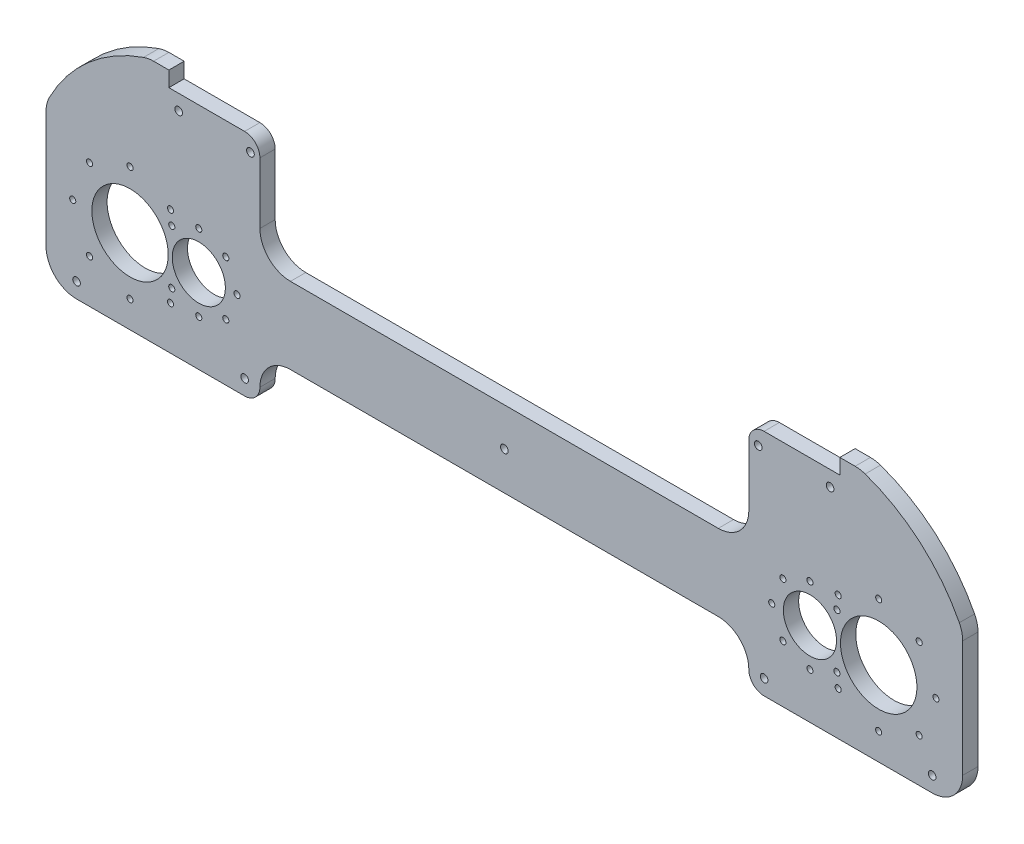
SolidWorks part; units mm, degrees
material "ABS"
ref_plane "Front Plane" through (0, 0, 0) normal (0, 0, 1) x (1, 0, 0)
ref_plane "Top Plane" through (0, 0, 0) normal (0, 1, 0) x (1, 0, 0)
ref_plane "Right Plane" through (0, 0, 0) normal (1, 0, 0) x (0, 0, -1)
sketch "Sketch1" plane through (0, 0, 0) normal (0, 0, 1) x (1, 0, 0)
  line L0 (-145.7836, 66.675) -> (145.7836, 66.675)
  line L1 (-190.5, 26.1817) -> (-190.5, -22.225)
  line L4 (0, 0) -> (0, 100.7987) construction
  line L5 (-177.8, -34.925) -> (177.8, -34.925)
  line L6 (190.5, 26.1817) -> (190.5, -22.225)
  line L7 (-190.5, 34.925) -> (190.5, -34.925) construction
  line L8 (-190.5, -34.925) -> (190.5, 34.925) construction
  arc A0 (177.8, -34.925) -> (190.5, -22.225) centre (177.8, -22.225) ccw
  arc A1 (149.9577, 65.9694) -> (189.0889, 31.9999) centre (127, 0) cw
  circle A2 centre (-127, 0) radius 3.175
  circle A3 centre (127, 0) radius 3.175
  arc A4 (-177.8, -34.925) -> (-190.5, -22.225) centre (-177.8, -22.225) cw
  arc A5 (190.5, 26.1817) -> (189.0889, 31.9999) centre (177.8, 26.1817) ccw
  arc A6 (-149.9577, 65.9694) -> (-189.0889, 31.9999) centre (-127, 0) ccw
  arc A7 (149.9577, 65.9694) -> (145.7836, 66.675) centre (145.7836, 53.975) ccw
  arc A8 (-190.5, 26.1817) -> (-189.0889, 31.9999) centre (-177.8, 26.1817) cw
  arc A9 (-145.7836, 66.675) -> (-149.9577, 65.9694) centre (-145.7836, 53.975) ccw
  point P0 (0, 0)
  point P22 (190.5, 29.0994)
  point P27 (147.8199, 66.675)
  point P30 (-190.5, 29.0994)
  point P33 (-147.8199, 66.675)
  dimension "D3" = 6.35
  dimension "D4" = 6.35
  dimension "D6" = 66.675
  dimension "D7" = 12.7
  dimension "D2" = 381
  dimension "D5" = 12.7
  dimension "D1" = 69.85
  dimension "D8" = 139.7
extrude "Boss-Extrude1" add sketch "Sketch1" along normal mid plane 6.35
sketch "Sketch2" plane through (0, 0, 3.175) normal (0, 0, 1) x (1, 0, 0)
  line L0 (-127, 0) -> (-207.737, 0) construction
  line L4 (0, 0) -> (0, 93.9723) construction
  circle A0 centre (-127, 0) radius 11.049
  circle A1 centre (-155.575, 0) radius 15.875
  circle A2 centre (127, 0) radius 15.875 construction
  circle A3 centre (155.575, 0) radius 23.8125 construction
  circle A4 centre (-155.575, 0) radius 23.8125 construction
  circle A5 centre (-127, 0) radius 15.875 construction
  circle A6 centre (-155.575, 23.8125) radius 1.27
  circle A7 centre (-138.737, 16.838) radius 1.27
  circle A8 centre (-131.7625, 0) radius 1.27 [skipped]
  circle A9 centre (-138.737, -16.838) radius 1.27
  circle A10 centre (-155.575, -23.8125) radius 1.27
  circle A11 centre (-172.413, -16.838) radius 1.27
  circle A12 centre (-179.3875, 0) radius 1.27
  circle A13 centre (-172.413, 16.838) radius 1.27
  circle A14 centre (-127, 15.875) radius 1.27
  circle A15 centre (-115.7747, 11.2253) radius 1.27
  circle A16 centre (-111.125, 0) radius 1.27
  circle A17 centre (-115.7747, -11.2253) radius 1.27
  circle A18 centre (-127, -15.875) radius 1.27
  circle A19 centre (-138.2253, -11.2253) radius 1.27
  circle A20 centre (138.2253, 11.2253) radius 1.27
  circle A21 centre (-138.2253, 11.2253) radius 1.27
  circle A22 centre (-142.875, 0) radius 1.27 [skipped]
  circle A23 centre (138.2253, -11.2253) radius 1.27
  circle A24 centre (127, -15.875) radius 1.27
  circle A25 centre (115.7747, -11.2253) radius 1.27
  circle A26 centre (111.125, 0) radius 1.27
  circle A27 centre (115.7747, 11.2253) radius 1.27
  circle A28 centre (127, 15.875) radius 1.27
  circle A29 centre (172.413, 16.838) radius 1.27
  circle A30 centre (179.3875, 0) radius 1.27
  circle A31 centre (172.413, -16.838) radius 1.27
  circle A32 centre (155.575, -23.8125) radius 1.27
  circle A33 centre (138.737, -16.838) radius 1.27
  circle A34 centre (138.737, 16.838) radius 1.27
  circle A35 centre (155.575, 23.8125) radius 1.27
  circle A36 centre (155.575, 0) radius 15.875
  circle A37 centre (127, 0) radius 11.049
  dimension "D2" = 28.575
  dimension "D3" = 31.75
  dimension "D4" = 31.75
  dimension "D5" = 47.625
  dimension "D6" = 2.54
  dimension "D1" = 22.098
  dimension "D8" = 2.54
  dimension "D7" = 8
  dimension "D9" = 8
extrude "Cut-Extrude1" cut sketch "Sketch2" against normal through all
sketch "Sketch5" plane through (0, 0, 3.175) normal (0, 0, 1) x (1, 0, 0)
  line L0 (145.7836, 66.675) -> (-145.7836, 66.675) construction
  line L1 (-88.9, 15.875) -> (88.9, 15.875)
  line L2 (-101.6, 28.575) -> (-101.6, 66.675)
  line L3 (-101.6, 66.675) -> (101.6, 66.675)
  line L4 (101.6, 28.575) -> (101.6, 66.675)
  line L5 (-101.6, 15.875) -> (101.6, 66.675) construction
  line L6 (-101.6, 66.675) -> (101.6, 15.875) construction
  line L7 (0, 0) -> (0, 128.2224) construction
  arc A0 (101.6, 28.575) -> (88.9, 15.875) centre (88.9, 28.575) cw
  arc A1 (-88.9, 15.875) -> (-101.6, 28.575) centre (-88.9, 28.575) cw
  point P0 (0, 41.275)
  dimension "D3" = 12.7
  dimension "D1" = 50.8
  dimension "D2" = 203.2
extrude "ITC_Cutout" cut sketch "Sketch5" against normal through all
sketch "Sketch6" plane through (0, 0, 3.175) normal (0, 0, 1) x (1, 0, 0)
  line L0 (-101.6, 66.675) -> (-145.7836, 66.675) construction
  line L1 (-71.9103, 66.675) -> (-139.4336, 66.675)
  line L2 (-71.9103, 66.675) -> (-71.9103, 60.325)
  line L3 (-71.9103, 60.325) -> (-139.4336, 60.325)
  line L4 (-139.4336, 66.675) -> (-139.4336, 60.325)
  line L5 (0, 0) -> (0, 132.6418) construction
  line L6 (139.4336, 66.675) -> (139.4336, 60.325)
  line L7 (71.9103, 60.325) -> (139.4336, 60.325)
  line L8 (71.9103, 66.675) -> (71.9103, 60.325)
  line L9 (71.9103, 66.675) -> (139.4336, 66.675)
  dimension "D1" = 6.35
  dimension "D2" = 6.35
extrude "Cut-Extrude3" cut sketch "Sketch6" against normal through all
fillet "Fillet1" radius 6.35 2 edges at (101.6, 60.325, 0) (-101.6, 60.325, 0)
sketch "Sketch7" plane through (0, 0, 3.175) normal (0, 0, 1) x (1, 0, 0)
  line L0 (0, 38.9819) -> (0, -79.3414) construction
  line L1 (-177.8, -34.925) -> (177.8, -34.925) construction
  line L2 (-88.9, -15.875) -> (88.9, -15.875)
  line L3 (-101.6, -28.575) -> (-101.6, -34.925)
  line L4 (-101.6, -34.925) -> (101.6, -34.925)
  line L5 (101.6, -28.575) -> (101.6, -34.925)
  line L6 (-101.6, -15.875) -> (101.6, -34.925) construction
  line L7 (-101.6, -34.925) -> (101.6, -15.875) construction
  line L8 (-101.6, 53.975) -> (-101.6, 28.575) construction
  arc A0 (101.6, -28.575) -> (88.9, -15.875) centre (88.9, -28.575) ccw
  arc A1 (-88.9, -15.875) -> (-101.6, -28.575) centre (-88.9, -28.575) ccw
  point P3 (0, -25.4)
  dimension "D2" = 12.7
  dimension "D1" = 19.05
extrude "Cut-Extrude4" cut sketch "Sketch7" against normal through all
fillet "Fillet2" radius 6.35 2 edges at (101.6, -34.925, 0) (-101.6, -34.925, 0)
sketch "Sketch8" plane through (0, 0, 3.175) normal (0, 0, 1) x (1, 0, 0)
  line L0 (-139.4336, 60.325) -> (-107.95, 60.325) construction
  line L1 (-139.4336, 66.675) -> (-139.4336, 60.325) construction
  line L2 (0, 0) -> (0, 74.8203) construction
  circle A0 centre (-135.3696, 53.975) radius 1.5875
  circle A1 centre (-105.5246, 53.975) radius 1.5875
  circle A2 centre (105.5246, 53.975) radius 1.5875
  circle A3 centre (135.3696, 53.975) radius 1.5875
  dimension "D1" = 3.175
  dimension "D3" = 3.175
  dimension "D2" = 6.35
  dimension "D4" = 29.845
  dimension "D5" = 4.064
extrude "Cut-Extrude5" cut sketch "Sketch8" against normal through all
sketch "Sketch10" plane through (0, 0, 3.175) normal (0, 0, 1) x (1, 0, 0)
  line L0 (0, 50.0636) -> (0, -61.6077) construction
  line L1 (-177.8, -34.925) -> (-107.95, -34.925) construction
  circle A0 centre (-177.8, -28.575) radius 1.5875
  circle A1 centre (-107.95, -28.575) radius 1.5875
  circle A2 centre (107.95, -28.575) radius 1.5875
  circle A3 centre (177.8, -28.575) radius 1.5875
  circle A4 centre (0, 0) radius 1.5875
  dimension "D1" = 3.175
  dimension "D4" = 3.175
  dimension "D6" = 3.175
  dimension "D2" = 6.35
  dimension "D3" = 177.8
  dimension "D5" = 107.95
extrude "Cut-Extrude6" cut sketch "Sketch10" against normal through all
equation "\"D3@Sketch8\" = \"D1@Sketch8\""
